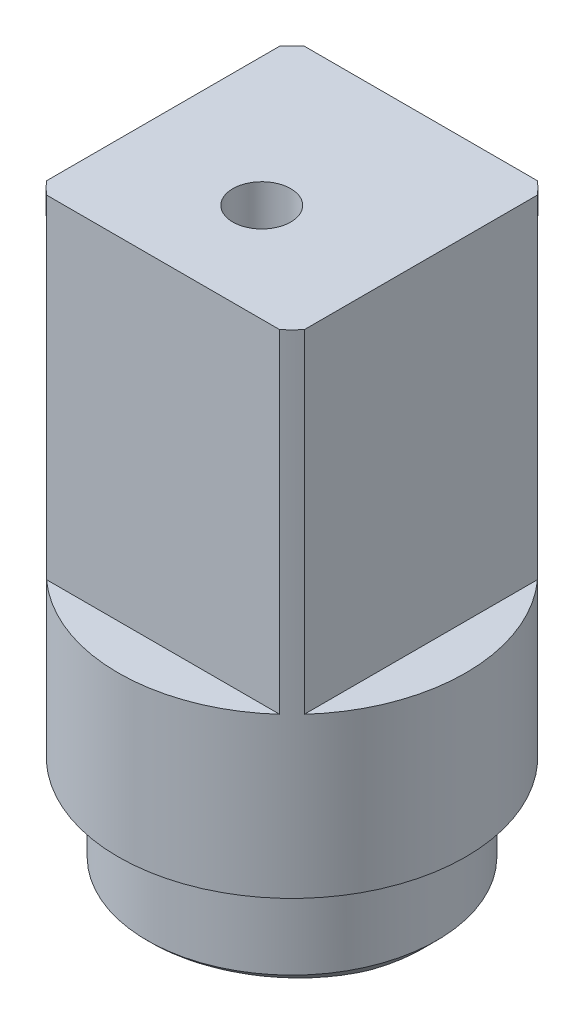
SolidWorks part; units mm, degrees
ref_plane "Front Plane" through (0, 0, 0) normal (0, 0, 1) x (1, 0, 0)
ref_plane "Top Plane" through (0, 0, 0) normal (0, 1, 0) x (1, 0, 0)
ref_plane "Right Plane" through (0, 0, 0) normal (1, 0, 0) x (0, 0, -1)
sketch "Sketch1" plane through (0, 0, 0) normal (0, 1, 0) x (1, 0, 0)
  circle A0 centre (0, 0) radius 6
extrude "Boss-Extrude1" add sketch "Sketch1" along normal blind 17
sketch "Sketch2" plane through (0, 17, 0) normal (0, 1, 0) x (1, 0, 0)
  line L1 (4.45, -4.45) -> (-4.45, -4.45)
  line L2 (4.45, -4.45) -> (4.45, 4.45)
  line L3 (4.45, 4.45) -> (-4.45, 4.45)
  line L4 (-4.45, -4.45) -> (-4.45, 4.45)
  line L5 (4.45, -4.45) -> (-4.45, 4.45) construction
  line L6 (4.45, 4.45) -> (-4.45, -4.45) construction
  point P0 (0, 0)
extrude "Cut-Extrude1" cut sketch "Sketch2" against normal blind 11.5 flip side to cut
sketch "Sketch3" plane through (0, 0, 0) normal (0, -1, 0) x (1, 0, 0)
  circle A0 centre (0, 0) radius 5
  dimension "D1" = 10
extrude "Boss-Extrude2" add sketch "Sketch3" along normal blind 3.5
sketch "Sketch4" plane through (0, -7.3478, 1) normal (1, 0, 0) x (0, 0, -1)
  line L0 (0, 5.75) -> (0, -5.75) construction
  line L1 (0, 5.75) -> (0, -5.75)
  arc A0 (0, 5.75) -> (0, -5.75) centre (0, 0) ccw
  dimension "D1" = 11.5
revolve "Cut-Revolve2" cut sketch "Sketch4" angle 360 about L0
sketch "Sketch5" plane through (0, 0, 0) normal (1, 0, 0) x (0, 0, -1)
  line L0 (-6, 0) -> (6, 0) construction
  line L2 (5, -3.5) -> (3.5, -3.5)
  line L3 (5, -3.5) -> (5, 0)
  line L4 (5, 0) -> (3.5, 0)
  line L5 (3.5, -3.5) -> (3.5, 0)
  line L6 (5, -3.5) -> (5, 0) construction
  point P4 (5, 0)
  dimension "D1" = 1.5
extrude "Cut-Extrude2" cut sketch "Sketch5" against normal through all both and the other way through all
fillet "Fillet2" radius 1 1 edges at (0, 0, -3.5)
sketch "Sketch6" plane through (0, -3.5, 0) normal (0, -1, 0) x (1, 0, 0)
  line L1 (2.1, -2.1) -> (-2.1, -2.1)
  line L2 (3.1, -1.1) -> (3.1, 3.1)
  line L3 (2.1, 4.1) -> (-2.1, 4.1)
  line L4 (-3.1, -1.1) -> (-3.1, 3.1)
  line L5 (3.1, -2.1) -> (-3.1, 4.1) construction
  line L6 (3.1, 4.1) -> (-3.1, -2.1) construction
  arc A0 (-3.1, -1.1) -> (-2.1, -2.1) centre (-2.1, -1.1) ccw
  arc A1 (2.1, -2.1) -> (3.1, -1.1) centre (2.1, -1.1) ccw
  arc A2 (3.1, 3.1) -> (2.1, 4.1) centre (2.1, 3.1) ccw
  arc A3 (-2.1, 4.1) -> (-3.1, 3.1) centre (-2.1, 3.1) ccw
  point P0 (0, 1)
  dimension "D3" = 1
  dimension "D1" = 1
  dimension "D2" = 6.2
extrude "Cut-Extrude3" cut sketch "Sketch6" against normal blind 7
sketch "Sketch7" plane through (0, 3.5, 0) normal (0, -1, 0) x (1, 0, 0)
  line L0 (-3.1, -1.1) -> (-3.1, 3.1) construction
  line L1 (2.1, -1.1) -> (-2.1, -1.1)
  line L2 (3.1, -0.1) -> (3.1, 2.1)
  line L3 (2.1, 3.1) -> (-2.1, 3.1)
  line L4 (-3.1, -0.1) -> (-3.1, 2.1)
  line L5 (3.1, -1.1) -> (-3.1, 3.1) construction
  line L6 (3.1, 3.1) -> (-3.1, -1.1) construction
  arc A0 (-3.1, -0.1) -> (-2.1, -1.1) centre (-2.1, -0.1) ccw
  arc A1 (2.1, -1.1) -> (3.1, -0.1) centre (2.1, -0.1) ccw
  arc A2 (3.1, 2.1) -> (2.1, 3.1) centre (2.1, 2.1) ccw
  arc A3 (-2.1, 3.1) -> (-3.1, 2.1) centre (-2.1, 2.1) ccw
  point P0 (0, 1)
  point P7 (0.1989, 2.4108)
  dimension "D3" = 1
  dimension "D1" = 1
  dimension "D2" = 4.2
extrude "Cut-Extrude4" cut sketch "Sketch7" against normal blind 8 contours L3 A3 L4 A0 L1 A1 L2 A2
sketch "Sketch8" plane through (0, 11.5, 0) normal (0, -1, 0) x (1, 0, 0)
  circle A0 centre (0, 1.0436) radius 1
  dimension "D1" = 2
extrude "Cut-Extrude5" cut sketch "Sketch8" against normal through all contours A0
chamfer "Chamfer1" distance 0.5 angle 45 3 edges at (-4.9924, -3.5, 0.2754) (0, -3.5, -3.5) (4.9924, -3.5, 0.2754)
